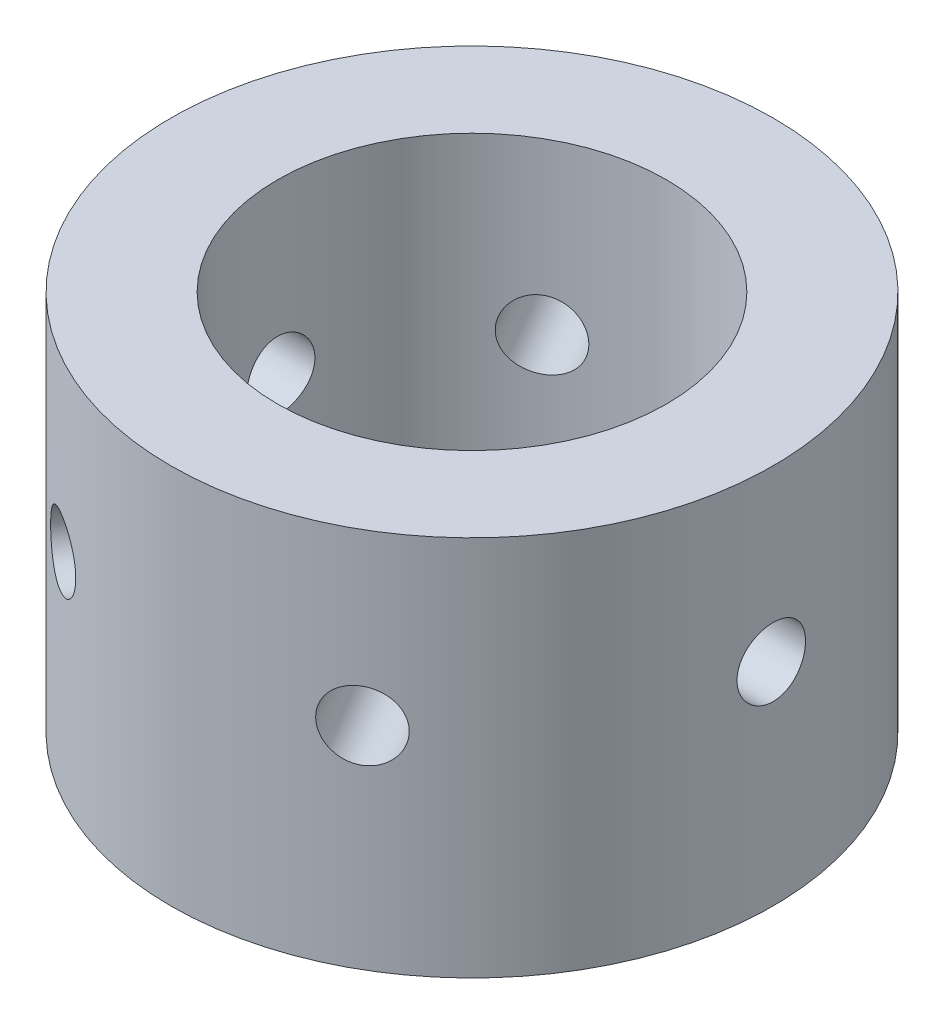
SolidWorks part; units mm, degrees
ref_plane "Front Plane" through (0, 0, 0) normal (0, 0, 1) x (1, 0, 0)
ref_plane "Top Plane" through (0, 0, 0) normal (0, 1, 0) x (1, 0, 0)
ref_plane "Right Plane" through (0, 0, 0) normal (1, 0, 0) x (0, 0, -1)
sketch "Sketch2" plane through (0, 0, 0) normal (0, 0, 1) x (1, 0, 0)
  line L0 (0, 0) -> (0, 56.8921) construction
  line L1 (-34.8996, 44.1706) -> (-22.5219, 44.1706)
  line L2 (-34.8996, 44.1706) -> (-34.8996, 0)
  line L3 (-34.8996, 0) -> (-22.5219, 0)
  line L4 (-22.5219, 44.1706) -> (-22.5219, 0)
  dimension "D1" = 34.8996
  dimension "D2" = 22.5219
  dimension "D3" = 44.1706
revolve "Revolve1" add sketch "Sketch2" angle 360 about L0
ref_plane "Plane1" through (34.8996, 0, 0) normal (1, 0, 0) x (0, 0, -1)
sketch "Sketch5" plane through (34.8996, 0, 0) normal (1, 0, 0) x (0, 0, -1)
  line L0 (22.5219, 44.1706) -> (-22.5219, 44.1706) construction
  point P0 (0, 24.4856)
  point P1 (0, 0)
  point P2 (0, 24.4856)
  point P4 (0, 0)
  point P5 (0, 0)
  point P6 (0, 0)
  point P7 (0, 0)
  point P8 (0, 0)
  dimension "D1" = 19.685
hole_wizard "3/8-16 Tapped Hole2" positions "Sketch11" profile "Sketch12" tap size "3/8-16" standard "ANSI Inch" end condition up to next
sketch "Sketch11" plane through (34.8996, 0, 0) normal (1, 0, 0) x (0, 0, -1)
  line L0 (0, 0) -> (0, 49.9183) construction
  line L2 (22.5219, 44.1706) -> (-22.5219, 44.1706) construction
  point P0 (0, 24.4856)
  point P8 (0, 0)
  dimension "D1" = 19.685
sketch "Sketch12" plane through (34.8996, 24.4856, 0) normal (0, 1, 0) x (0, 0, -1)
  line L0 (0, 0) -> (0, 12.3777)
  line L1 (0, 12.3777) -> (3.9687, 12.3777)
  line L2 (3.9687, 12.3777) -> (3.9687, 0)
  line L5 (3.9687, 0) -> (0, 0)
  line L11 (0, -6.35) -> (0, 107.95) construction
  dimension "Thru Tap Drill Dia." = 7.9375
  dimension "Thru Tap Drill Depth" = 12.3777
cosmetic thread "Hole Thread4" parameters "D2"=9.525
ref_axis "Axis1" through (0, 44.1706, 0) along (0, -1, 0)
pattern_circular "CirPattern1" count 6 every 60 about axis through (0, 44.1706, 0) along (0, -1, 0) of "3/8-16 Tapped Hole2"
cosmetic thread "Hole Thread5" parameters "D2"=9.525
cosmetic thread "Hole Thread6" parameters "D2"=9.525
cosmetic thread "Hole Thread7" parameters "D2"=9.525
cosmetic thread "Hole Thread8" parameters "D2"=9.525
cosmetic thread "Hole Thread9" parameters "D2"=9.525
